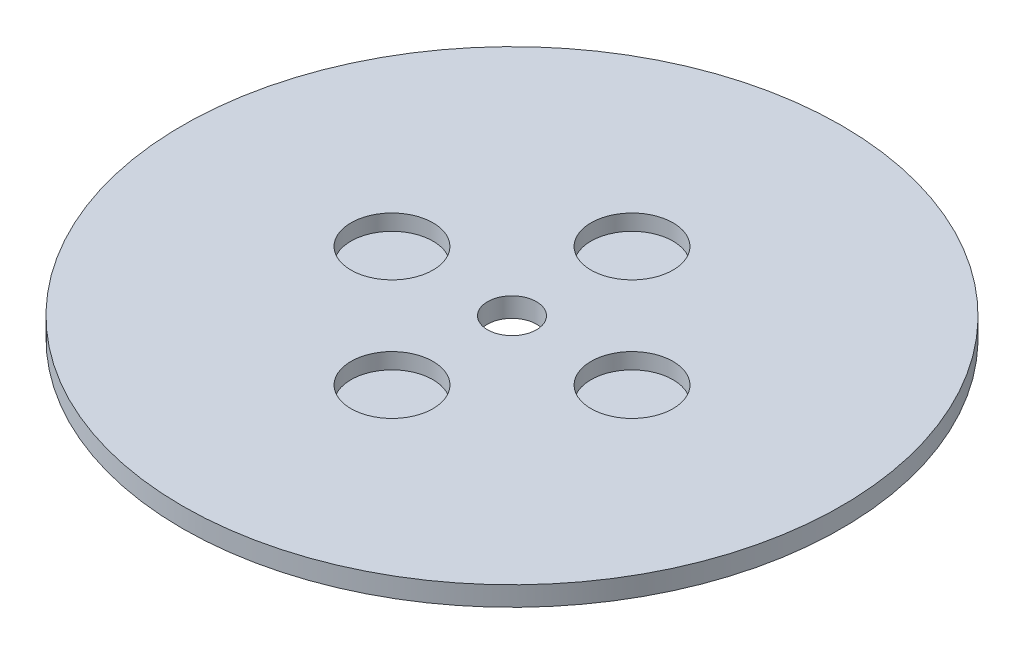
SolidWorks part; units mm, degrees
ref_plane "Front Plane" through (0, 0, 0) normal (0, 0, 1) x (1, 0, 0)
ref_plane "Top Plane" through (0, 0, 0) normal (0, 1, 0) x (1, 0, 0)
ref_plane "Right Plane" through (0, 0, 0) normal (1, 0, 0) x (0, 0, -1)
sketch "Sketch1" plane through (0, 0, 0) normal (0, 1, 0) x (1, 0, 0)
  circle A0 centre (0, 0) radius 67.5
  dimension "FLANGE_OD" = 135
extrude "Boss-Extrude1" add sketch "Sketch1" along normal blind 4
sketch "Sketch2" plane through (0, 0, 0) normal (0, 1, 0) x (1, 0, 0)
  circle A0 centre (0, 0) radius 5
  dimension "BORE_D" = 10
extrude "Cut-Extrude1" cut sketch "Sketch2" along normal through all
sketch "Sketch3" plane through (0, 4, 0) normal (0, 1, 0) x (1, 0, 0)
  circle A0 centre (0, 0) radius 24.5816 construction
  circle A1 centre (-24.5816, 0) radius 8.3967
  dimension "BOLT_D" = 16.7933
  dimension "BOLT_PCD" = 49.1632
extrude "Cut-Extrude2" cut sketch "Sketch3" against normal blind 3.251
pattern_circular "CirPattern1" count 4 over 360 about axis through (0, 0, 0) along (0, 1, 0) of "Cut-Extrude2"
